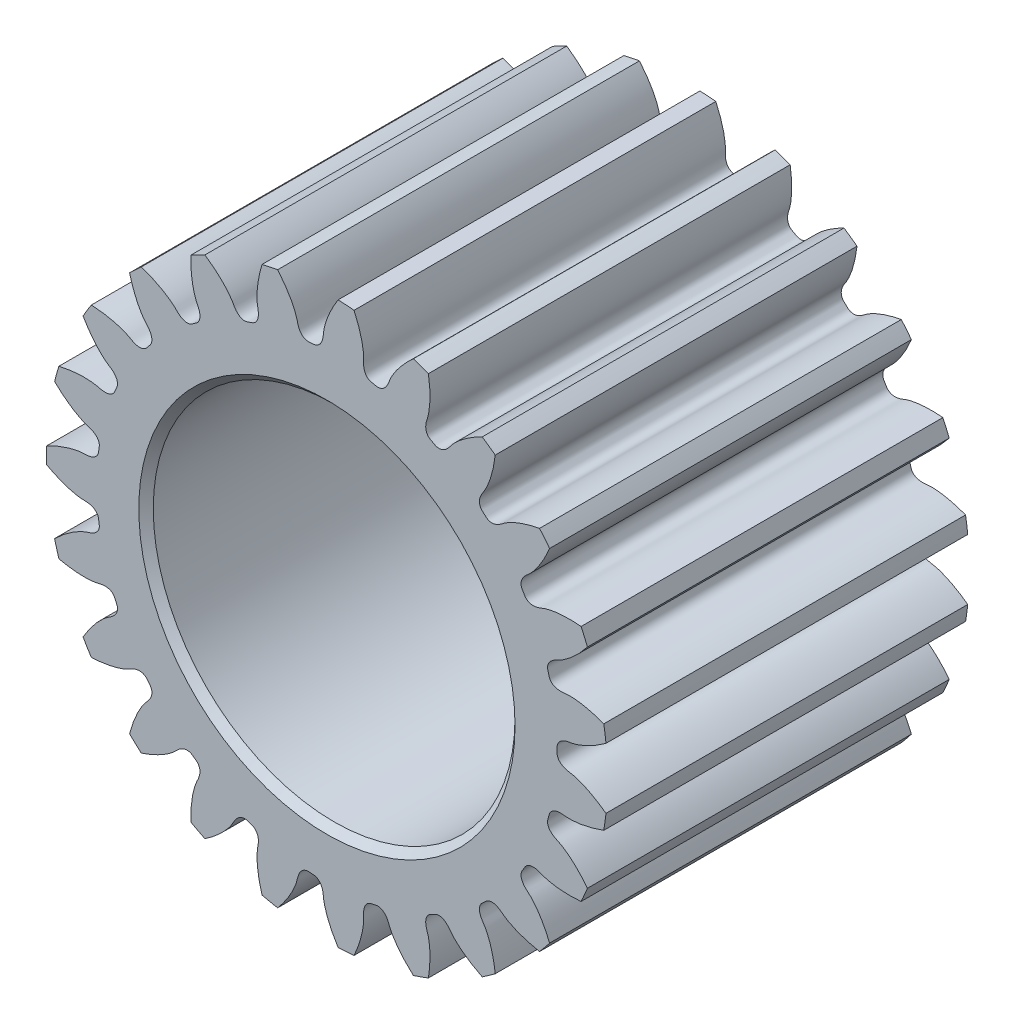
SolidWorks part; units mm, degrees
ref_plane "Front Plane" through (0, 0, 0) normal (0, 0, 1) x (1, 0, 0)
ref_plane "Top Plane" through (0, 0, 0) normal (0, 1, 0) x (1, 0, 0)
ref_plane "Right Plane" through (0, 0, 0) normal (1, 0, 0) x (0, 0, -1)
ref_axis "Axis1" through (0, 0, 55) along (0, 0, -1)
sketch "SketchRevolvePlanet_Revolving_Follower01" plane through (0, 0, 0) normal (1, 0, 0) x (0, 0, -1)
  line L0 (0, 0) -> (25.4, 0) construction
  line L1 (-6.35, 0) -> (-6.35, 9.8529)
  line L2 (-6.35, 9.8529) -> (6.35, 9.8529)
  line L3 (6.35, 9.8529) -> (6.35, 0)
  line L4 (6.35, 0) -> (-6.35, 0)
  dimension "Side1" = 6.35
  dimension "OutsideRadius" = 9.8529
  dimension "Side2" = 6.35
revolve "Planet_Revolving_Follower01" add sketch "SketchRevolvePlanet_Revolving_Follower01" angle 360 about L0
sketch "SketchToothPlanet_Revolving_Follower01" plane through (0, 0, 0) normal (0, 0, 1) x (1, 0, 0)
  arc A0 (9.832, 1.0908) -> (9.832, -1.0908) centre (0, 0) cw
  spline S0 degree 3 poles (9.832, -1.0908) (9.7221, -1.0083) (9.5752, -0.9071) (9.3896, -0.7956) (9.2892, -0.7392) (9.1938, -0.6893) (9.1036, -0.6454) (9.0189, -0.6073) (8.9401, -0.5746) (8.8672, -0.5468) (8.8006, -0.5236) (8.7404, -0.5047) (8.6868, -0.4895) (8.6399, -0.4777) (8.6001, -0.4689) (8.5437, -0.4582) (8.4928, -0.4521) (8.4465, -0.4423) (8.425, -0.4373) (8.404, -0.4318) (8.3834, -0.4258) (8.3632, -0.4193) (8.3434, -0.4122) (8.324, -0.4046) (8.3049, -0.3963) (8.2861, -0.3873) (8.2675, -0.3776) (8.2492, -0.3669) (8.2312, -0.3552) (8.2133, -0.3424) (8.1957, -0.3283) (8.1784, -0.3126) (8.1614, -0.2951) (8.145, -0.2757) (8.1295, -0.2541) (8.1151, -0.23) (8.1024, -0.2036) (8.0918, -0.1747) (8.084, -0.1438) (8.0799, -0.1134) (8.0781, -0.0653) (8.0804, 0) (8.0781, 0.0653) (8.0799, 0.1134) (8.084, 0.1438) (8.0918, 0.1747) (8.1024, 0.2036) (8.1151, 0.23) (8.1295, 0.2541) (8.145, 0.2757) (8.1614, 0.2951) (8.1784, 0.3126) (8.1957, 0.3283) (8.2133, 0.3424) (8.2312, 0.3552) (8.2492, 0.3669) (8.2675, 0.3776) (8.2861, 0.3873) (8.3049, 0.3963) (8.324, 0.4046) (8.3434, 0.4122) (8.3632, 0.4193) (8.3834, 0.4258) (8.404, 0.4318) (8.425, 0.4373) (8.4465, 0.4423) (8.4928, 0.4521) (8.5437, 0.4582) (8.6001, 0.4689) (8.6399, 0.4777) (8.6868, 0.4895) (8.7404, 0.5047) (8.8006, 0.5236) (8.8672, 0.5468) (8.9401, 0.5746) (9.0189, 0.6073) (9.1036, 0.6454) (9.1938, 0.6893) (9.2892, 0.7392) (9.3896, 0.7956) (9.5752, 0.9071) (9.7221, 1.0083) (9.832, 1.0908) knots 0 0 0 0 0.094201 0.122209 0.14852 0.173133 0.196048 0.217267 0.236787 0.25461 0.270736 0.285165 0.297895 0.308929 0.318265 0.325903 0.34824 0.353362 0.3584 0.363363 0.36826 0.373101 0.377899 0.382666 0.38742 0.392177 0.396959 0.40179 0.406696 0.411708 0.416859 0.422185 0.427725 0.433517 0.439595 0.445983 0.452694 0.459717 0.467016 0.474526 0.480668 0.5 0.519332 0.525474 0.532984 0.540283 0.547306 0.554017 0.560405 0.566483 0.572275 0.577815 0.583141 0.588292 0.593304 0.59821 0.603041 0.607823 0.61258 0.617334 0.622101 0.626899 0.63174 0.636637 0.6416 0.646638 0.65176 0.674097 0.681735 0.691071 0.702105 0.714835 0.729264 0.74539 0.763213 0.782733 0.803952 0.826867 0.85148 0.877791 0.905799 1 1 1 1
extrude "ToothExtrudeCutPlanet_Revolving_Follower01" cut sketch "SketchToothPlanet_Revolving_Follower01" against normal blind 6.35 and the other way blind 6.35
ref_axis "Axis2" through (10.8796, 0, 0) along (-1, 0, 0)
ref_plane "Plane1" through (0, 0, 0) normal (0, 0, -1) x (1, 0, 0)
pattern_circular "PatternPlanet_Revolving_Follower01" count 23 every 15.652 about axis through (0, 0, 55) along (0, 0, -1) of "ToothExtrudeCutPlanet_Revolving_Follower01"
sketch "BoreRevolveSketch" plane through (0, 0, 0) normal (1, 0, 0) x (0, 0, -1)
  line L0 (0, 0) -> (25.4, 0) construction
  line L1 (-6.35, 0) -> (6.35, 0)
  line L2 (6.35, 0) -> (6.35, 6.604)
  line L3 (6.35, 6.604) -> (6.096, 6.35)
  line L4 (6.096, 6.35) -> (-6.096, 6.35)
  line L5 (-6.096, 6.35) -> (-6.35, 6.604)
  line L6 (-6.35, 6.604) -> (-6.35, 0)
  dimension "BoreSide1" = 6.35
  dimension "TaperSide1" = 6.604
  dimension "Chamfer1X" = 0.254
  dimension "Chamfer1Y" = 0.254
  dimension "BoreSide2" = 6.35
  dimension "TaperSide2" = 6.604
revolve "BoreRevolveCut" cut sketch "BoreRevolveSketch" angle 360 about L0
sketch "AuxiliarySketchPlanet_Revolving_Follower01" plane through (0, 0, 0) normal (0, 0, 1) x (1, 0, 0)
  circle A0 centre (0, 0) radius 9.0647 construction
  circle A1 centre (0, 0) radius 8.518 construction
  circle A2 centre (0, 0) radius 8.5447 construction
  circle A3 centre (0, 0) radius 9.8529 construction
  circle A4 centre (0, 0) radius 8.0794 construction
  dimension "PitchDiameter" = 18.1294
  dimension "BaseDiameter" = 17.0361
  dimension "FormDiameter" = 17.0894
  dimension "MajorDiameter" = 19.7059
  dimension "MinorDiameter" = 16.1588
